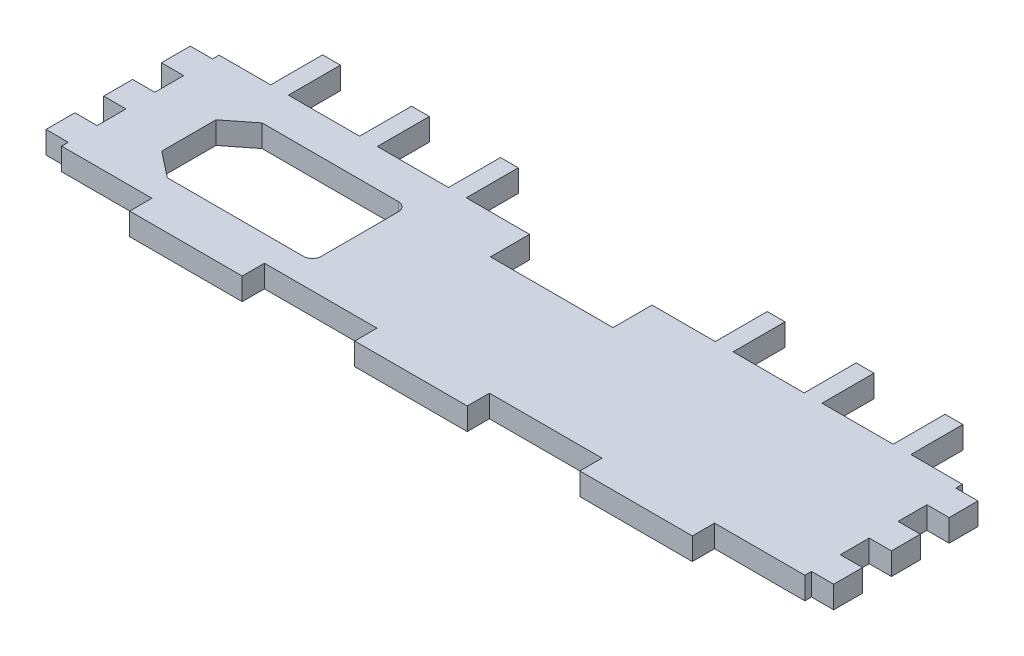
SolidWorks part; units mm, degrees
ref_plane "Front Plane" through (0, 0, 0) normal (0, 0, 1) x (1, 0, 0)
ref_plane "Top Plane" through (0, 0, 0) normal (0, 1, 0) x (1, 0, 0)
ref_plane "Right Plane" through (0, 0, 0) normal (1, 0, 0) x (0, 0, -1)
sketch "Sketch1" plane through (0, 0, 0) normal (0, 1, 0) x (1, 0, 0)
  line L48 (32.1429, 0) -> (32.1429, 6.35)
  line L49 (0, 0) -> (32.1429, 0)
  line L50 (0, 0) -> (0, 6.35)
  line L51 (0, 6.35) -> (32.1429, 6.35)
  line L52 (32.1429, 0) -> (32.1429, 6.35)
  line L53 (0, 0) -> (6.35, 0)
  line L54 (0, 0) -> (0, 8.2429)
  line L55 (0, 8.2429) -> (6.35, 8.2429)
  line L56 (6.35, 0) -> (6.35, 8.2429)
  line L57 (32.1429, 0) -> (64.2857, 0)
  line L58 (64.2857, 0) -> (64.2857, 6.35)
  line L59 (32.1429, 6.35) -> (64.2857, 6.35)
  line L60 (64.2857, 0) -> (64.2857, 6.35)
  line L61 (64.2857, 0) -> (96.4286, 0)
  line L62 (96.4286, 0) -> (96.4286, 6.35)
  line L63 (64.2857, 6.35) -> (96.4286, 6.35)
  line L64 (96.4286, 0) -> (96.4286, 6.35)
  line L65 (96.4286, 0) -> (128.5714, 0)
  line L66 (128.5714, 0) -> (128.5714, 6.35)
  line L67 (96.4286, 6.35) -> (128.5714, 6.35)
  line L72 (128.5714, 0) -> (128.5714, 6.35)
  line L73 (128.5714, 0) -> (160.7143, 0)
  line L74 (160.7143, 0) -> (160.7143, 6.35)
  line L75 (128.5714, 6.35) -> (160.7143, 6.35)
  line L76 (160.7143, 0) -> (160.7143, 6.35)
  line L77 (160.7143, 0) -> (192.8571, 0)
  line L78 (192.8571, 0) -> (192.8571, 6.35)
  line L79 (160.7143, 6.35) -> (192.8571, 6.35)
  line L80 (192.8571, 0) -> (192.8571, 6.35)
  line L81 (192.8571, 0) -> (225, 0)
  line L82 (225, 0) -> (225, 6.35)
  line L83 (192.8571, 6.35) -> (225, 6.35)
  line L84 (0, 8.2429) -> (0, 16.4857)
  line L85 (0, 8.2429) -> (6.35, 8.2429)
  line L86 (6.35, 8.2429) -> (6.35, 16.4857)
  line L87 (0, 16.4857) -> (6.35, 16.4857)
  line L88 (0, 16.4857) -> (0, 24.7286)
  line L89 (0, 16.4857) -> (6.35, 16.4857)
  line L90 (6.35, 16.4857) -> (6.35, 24.7286)
  line L91 (0, 24.7286) -> (6.35, 24.7286)
  line L98 (0, 24.7286) -> (0, 32.9714)
  line L99 (0, 24.7286) -> (6.35, 24.7286)
  line L100 (6.35, 24.7286) -> (6.35, 32.9714)
  line L101 (0, 32.9714) -> (6.35, 32.9714)
  line L102 (0, 32.9714) -> (0, 41.2143)
  line L103 (0, 32.9714) -> (6.35, 32.9714)
  line L104 (6.35, 32.9714) -> (6.35, 41.2143)
  line L105 (0, 41.2143) -> (6.35, 41.2143)
  line L106 (0, 41.2143) -> (0, 49.4571)
  line L107 (0, 41.2143) -> (6.35, 41.2143)
  line L108 (6.35, 41.2143) -> (6.35, 49.4571)
  line L109 (0, 49.4571) -> (6.35, 49.4571)
  line L110 (0, 49.4571) -> (0, 57.7)
  line L111 (0, 49.4571) -> (6.35, 49.4571)
  line L112 (6.35, 49.4571) -> (6.35, 57.7)
  line L113 (0, 57.7) -> (6.35, 57.7)
  line L114 (112.5, 0) -> (112.5, 671.069) construction
  line L115 (-187.856, 28.85) -> (254.8092, 28.85) construction
  line L116 (225, 8.2429) -> (218.65, 8.2429)
  line L117 (218.65, 0) -> (218.65, 8.2429)
  line L118 (225, 0) -> (218.65, 0)
  line L119 (225, 0) -> (225, 8.2429)
  line L120 (225, 49.4571) -> (218.65, 49.4571)
  line L121 (218.65, 49.4571) -> (218.65, 57.7)
  line L122 (225, 57.7) -> (218.65, 57.7)
  line L123 (225, 49.4571) -> (225, 57.7)
  line L124 (225, 41.2143) -> (218.65, 41.2143)
  line L125 (218.65, 41.2143) -> (218.65, 49.4571)
  line L126 (225, 49.4571) -> (218.65, 49.4571)
  line L127 (225, 41.2143) -> (225, 49.4571)
  line L128 (225, 8.2429) -> (218.65, 8.2429)
  line L129 (218.65, 8.2429) -> (218.65, 16.4857)
  line L130 (225, 16.4857) -> (218.65, 16.4857)
  line L131 (225, 8.2429) -> (225, 16.4857)
  line L132 (225, 32.9714) -> (218.65, 32.9714)
  line L133 (218.65, 32.9714) -> (218.65, 41.2143)
  line L134 (225, 41.2143) -> (218.65, 41.2143)
  line L135 (225, 32.9714) -> (225, 41.2143)
  line L136 (225, 24.7286) -> (218.65, 24.7286)
  line L137 (218.65, 24.7286) -> (218.65, 32.9714)
  line L138 (225, 32.9714) -> (218.65, 32.9714)
  line L139 (225, 24.7286) -> (225, 32.9714)
  line L140 (225, 16.4857) -> (218.65, 16.4857)
  line L141 (218.65, 16.4857) -> (218.65, 24.7286)
  line L142 (225, 24.7286) -> (218.65, 24.7286)
  line L143 (225, 16.4857) -> (225, 24.7286)
  line L144 (192.8571, 57.7) -> (225, 57.7)
  line L145 (225, 57.7) -> (225, 51.35)
  line L146 (192.8571, 51.35) -> (225, 51.35)
  line L147 (192.8571, 57.7) -> (192.8571, 51.35)
  line L148 (160.7143, 57.7) -> (192.8571, 57.7)
  line L149 (192.8571, 57.7) -> (192.8571, 51.35)
  line L150 (160.7143, 51.35) -> (192.8571, 51.35)
  line L151 (160.7143, 57.7) -> (160.7143, 51.35)
  line L152 (128.5714, 57.7) -> (160.7143, 57.7)
  line L153 (160.7143, 57.7) -> (160.7143, 51.35)
  line L154 (128.5714, 51.35) -> (160.7143, 51.35)
  line L155 (128.5714, 57.7) -> (128.5714, 51.35)
  line L156 (96.4286, 57.7) -> (128.5714, 57.7)
  line L157 (128.5714, 57.7) -> (128.5714, 51.35)
  line L158 (96.4286, 51.35) -> (128.5714, 51.35)
  line L159 (96.4286, 57.7) -> (96.4286, 51.35)
  line L160 (64.2857, 57.7) -> (96.4286, 57.7)
  line L161 (96.4286, 57.7) -> (96.4286, 51.35)
  line L162 (64.2857, 51.35) -> (96.4286, 51.35)
  line L163 (64.2857, 57.7) -> (64.2857, 51.35)
  line L164 (32.1429, 57.7) -> (64.2857, 57.7)
  line L165 (64.2857, 57.7) -> (64.2857, 51.35)
  line L166 (32.1429, 51.35) -> (64.2857, 51.35)
  line L167 (32.1429, 57.7) -> (32.1429, 51.35)
  line L168 (0, 51.35) -> (32.1429, 51.35)
  line L169 (32.1429, 57.7) -> (32.1429, 51.35)
  line L170 (0, 57.7) -> (32.1429, 57.7)
  line L171 (0, 57.7) -> (0, 51.35)
  point P56 (112.5, 6.35)
  point P58 (6.35, 28.85)
  dimension "D3" = 6.35
  dimension "D4" = 225
  dimension "D5" = 57.7
  dimension "D2" = 7
  dimension "D1" = 7
extrude "Boss-Extrude1" add sketch "Sketch1" along normal blind 6.35 contours L168 L112 L108 L104 L100 L90 L86 L56 L51 L59 L63 L67 L75 L79 L83 L117 L129 L141 L137 L133 L125 L121 L146 L150 L154 L158 L162 L166 | L156 L159 L158 L155 | L67 L62 L65 L66 | L79 L74 L77 L78 | L148 L151 L150 L147 | L164 L167 L166 L163 | L59 L48 L57 L58 | L87 L84 L55 L86 | L101 L98 L91 L100 | L109 L106 L105 L108 | L116 L131 L130 L129 | L136 L139 L132 L137 | L124 L127 L120 L125 region at (48.2143, 0, -3.175) region at (112.5, 0, -28.85) region at (112.5, 0, -3.175) region at (3.175, 0, -12.3643) region at (176.7857, 0, -3.175) region at (3.175, 0, -28.85) region at (3.175, 0, -45.3357) region at (221.825, 0, -12.3643) region at (48.2143, 0, -54.525) region at (221.825, 0, -28.85) region at (112.5, 0, -54.525) region at (221.825, 0, -45.3357) region at (176.7857, 0, -54.525)
sketch "Sketch2" plane through (0, 6.35, 0) normal (0, 1, 0) x (1, 0, 0)
  line L0 (32.1429, 57.7) -> (64.2857, 57.7) construction
  line L1 (6.35, 51.35) -> (218.65, 51.35)
  line L2 (6.35, 51.35) -> (6.35, 57.7)
  line L3 (6.35, 57.7) -> (218.65, 57.7)
  line L4 (218.65, 51.35) -> (218.65, 57.7)
  line L5 (46.46, 66.2) -> (46.46, 57.7)
  line L6 (21.06, 66.2) -> (26.14, 66.2)
  line L7 (21.06, 66.2) -> (21.06, 57.7)
  line L8 (21.06, 57.7) -> (26.14, 57.7)
  line L9 (26.14, 66.2) -> (26.14, 57.7)
  line L10 (46.46, 66.2) -> (51.54, 66.2)
  line L11 (51.54, 66.2) -> (51.54, 57.7)
  line L12 (46.46, 57.7) -> (51.54, 57.7)
  line L13 (71.86, 66.2) -> (71.86, 57.7)
  line L14 (71.86, 66.2) -> (76.94, 66.2)
  line L15 (76.94, 66.2) -> (76.94, 57.7)
  line L16 (71.86, 57.7) -> (76.94, 57.7)
  line L17 (97.26, 66.2) -> (97.26, 57.7)
  line L18 (97.26, 66.2) -> (102.34, 66.2)
  line L19 (102.34, 66.2) -> (102.34, 57.7)
  line L20 (97.26, 57.7) -> (102.34, 57.7)
  line L21 (122.66, 66.2) -> (122.66, 57.7)
  line L22 (122.66, 66.2) -> (127.74, 66.2)
  line L23 (127.74, 66.2) -> (127.74, 57.7)
  line L24 (122.66, 57.7) -> (127.74, 57.7)
  line L25 (148.06, 66.2) -> (148.06, 57.7)
  line L26 (148.06, 66.2) -> (153.14, 66.2)
  line L27 (153.14, 66.2) -> (153.14, 57.7)
  line L28 (148.06, 57.7) -> (153.14, 57.7)
  line L29 (173.46, 66.2) -> (173.46, 57.7)
  line L30 (173.46, 66.2) -> (178.54, 66.2)
  line L31 (178.54, 66.2) -> (178.54, 57.7)
  line L32 (173.46, 57.7) -> (178.54, 57.7)
  line L33 (198.86, 66.2) -> (198.86, 57.7)
  line L34 (198.86, 66.2) -> (203.94, 66.2)
  line L35 (203.94, 66.2) -> (203.94, 57.7)
  line L36 (198.86, 57.7) -> (203.94, 57.7)
  line L45 (224.26, 66.2) -> (224.26, 57.7) [skipped]
  line L46 (224.26, 66.2) -> (229.34, 66.2) [skipped]
  line L47 (229.34, 66.2) -> (229.34, 57.7) [skipped]
  line L48 (224.26, 57.7) -> (229.34, 57.7) [skipped]
  line L49 (249.66, 66.2) -> (249.66, 57.7) [skipped]
  line L50 (249.66, 66.2) -> (254.74, 66.2) [skipped]
  line L51 (254.74, 66.2) -> (254.74, 57.7) [skipped]
  line L52 (249.66, 57.7) -> (254.74, 57.7) [skipped]
  line L53 (112.5, 0) -> (112.5, 77.7946) construction
  line L55 (96.4286, 0) -> (128.5714, 0) construction
  line L56 (112.5, 66.2) -> (122.66, 66.2) construction
  line L57 (112.5, 66.2) -> (102.34, 66.2) construction
  point P44 (112.5, 0)
  point P46 (49, 66.2)
  point P47 (23.6, 66.2)
  dimension "D2" = 5.08
  dimension "D3" = 25.4
  dimension "D4" = 8.5
  dimension "D1" = 10
extrude "Boss-Extrude2" add sketch "Sketch2" against normal up to surface (6.35 mm away) contours L1 L4 L3 L2 | L9 L6 L7 L3 | L11 L10 L5 L3 | L15 L14 L13 L3 | L19 L18 L17 L3 | L35 L34 L33 L3 | L31 L30 L29 L3 | L21 L24 L23 L22 | L27 L28 L25 L26 region at (112.5, 6.35, -54.525) region at (23.6, 6.35, -61.95) region at (201.4, 6.35, -61.95) region at (49, 6.35, -61.95) region at (176, 6.35, -61.95) region at (74.4, 6.35, -61.95) region at (99.8, 6.35, -61.95) up to face at (112.5, 0, -28.85)
sketch "Sketch3" plane through (0, 6.35, 0) normal (0, 1, 0) x (1, 0, 0)
  line L1 (112.5, 0) -> (112.5, 57.7) construction
  line L2 (95, 40.2) -> (130, 40.2)
  line L3 (95, 40.2) -> (95, 66.2)
  line L4 (95, 66.2) -> (130, 66.2)
  line L5 (130, 40.2) -> (130, 66.2)
  line L6 (96.4286, 0) -> (128.5714, 0) construction
  line L7 (102.34, 57.7) -> (122.66, 57.7) construction
  line L8 (127.74, 57.7) -> (148.06, 57.7) construction
  line L9 (122.66, 66.2) -> (127.74, 66.2) construction
  point P10 (112.5, 66.2)
  dimension "D1" = 35
  dimension "D2" = 17.5
extrude "Cut-Extrude1" cut sketch "Sketch3" against normal through all
sketch "Sketch4" plane through (0, 6.35, 0) normal (0, 1, 0) x (1, 0, 0)
  line L0 (203.94, 66.2) -> (203.94, 57.7) construction
  line L1 (6.35, 57.7) -> (21.06, 57.7)
  line L2 (6.35, 57.7) -> (6.35, 51.35)
  line L3 (6.35, 51.35) -> (21.06, 51.35)
  line L4 (21.06, 57.7) -> (21.06, 51.35)
  line L5 (26.14, 57.7) -> (46.46, 57.7)
  line L6 (26.14, 57.7) -> (26.14, 51.35)
  line L7 (26.14, 51.35) -> (46.46, 51.35)
  line L8 (46.46, 57.7) -> (46.46, 51.35)
  line L9 (218.65, 57.7) -> (203.94, 57.7)
  line L10 (218.65, 57.7) -> (218.65, 51.35)
  line L11 (218.65, 51.35) -> (203.94, 51.35)
  line L12 (203.94, 57.7) -> (203.94, 51.35)
  line L13 (198.86, 57.7) -> (178.54, 57.7)
  line L14 (198.86, 57.7) -> (198.86, 51.35)
  line L15 (198.86, 51.35) -> (178.54, 51.35)
  line L16 (178.54, 57.7) -> (178.54, 51.35)
  line L17 (203.94, 57.7) -> (218.65, 57.7) construction
  dimension "D1" = 6.35
extrude "Cut-Extrude2" cut sketch "Sketch4" against normal up to surface (6.35 mm away) up to face at (112.5, 0, -37.3706)
sketch "Sketch5" plane through (0, 6.35, 0) normal (0, 1, 0) x (1, 0, 0)
  line L1 (51.54, 57.7) -> (71.86, 57.7)
  line L2 (51.54, 57.7) -> (51.54, 51.35)
  line L3 (51.54, 51.35) -> (71.86, 51.35)
  line L4 (71.86, 57.7) -> (71.86, 51.35)
  line L5 (76.94, 57.7) -> (95, 57.7)
  line L6 (76.94, 57.7) -> (76.94, 51.35)
  line L7 (76.94, 51.35) -> (95, 51.35)
  line L8 (95, 57.7) -> (95, 51.35)
  line L9 (153.14, 66.2) -> (153.14, 57.7) construction
  line L10 (130, 57.7) -> (148.06, 57.7)
  line L11 (130, 57.7) -> (130, 51.35)
  line L12 (130, 51.35) -> (148.06, 51.35)
  line L13 (148.06, 57.7) -> (148.06, 51.35)
  line L14 (153.14, 57.7) -> (173.46, 57.7)
  line L15 (153.14, 57.7) -> (153.14, 51.35)
  line L16 (153.14, 51.35) -> (173.46, 51.35)
  line L17 (173.46, 57.7) -> (173.46, 51.35)
  line L18 (148.06, 66.2) -> (148.06, 57.7) construction
  line L19 (71.86, 66.2) -> (71.86, 57.7) construction
  line L20 (26.14, 51.35) -> (46.46, 51.35) construction
  line L21 (173.46, 66.2) -> (173.46, 57.7) construction
extrude "Cut-Extrude3" cut sketch "Sketch5" against normal through all
sketch "Sketch7" plane through (0, 6.35, 0) normal (0, 1, 0) x (1, 0, 0)
  line L6 (70.7075, 16.1539) -> (70.7075, 38.1757)
  line L7 (68.1675, 40.7157) -> (29.2674, 40.7157)
  line L8 (29.2674, 40.7157) -> (21.8981, 34.9245)
  line L9 (21.8981, 34.9245) -> (21.8981, 19.4051)
  line L10 (68.1675, 13.6139) -> (29.2674, 13.6139)
  line L11 (29.2674, 13.6139) -> (21.8981, 19.4051)
  arc A2 (70.7075, 16.1539) -> (68.1675, 13.6139) centre (68.1675, 16.1539) cw
  arc A3 (70.7075, 38.1757) -> (68.1675, 40.7157) centre (68.1675, 38.1757) ccw
  point P2 (17.9781, 28.6877)
  point P3 (66.7876, 28.6877)
  point P4 (25.3475, 15.1368)
  point P5 (17.9781, 20.928)
  point P6 (0, 0)
extrude "Cut-Extrude5" cut sketch "Sketch7" against normal through all
